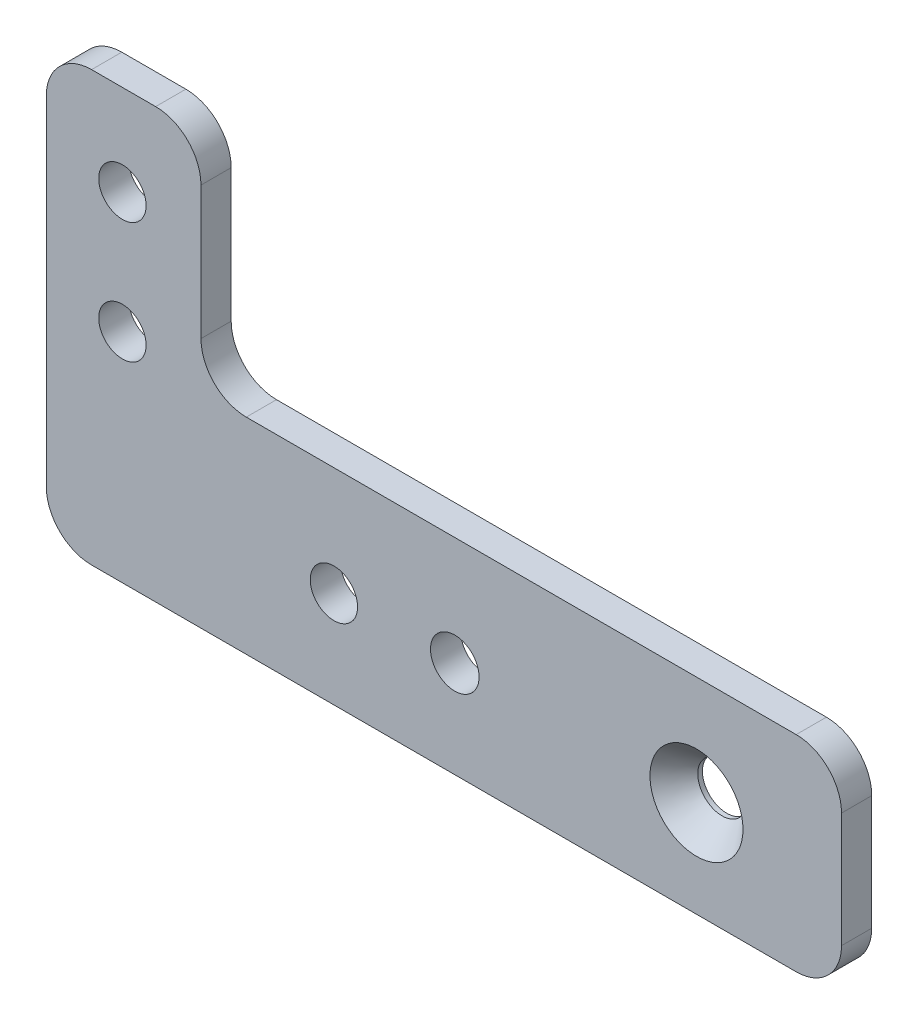
SolidWorks part; units mm, degrees
material "6061-T6 (SS)"
ref_plane "Front Plane" through (0, 0, 0) normal (0, 0, 1) x (1, 0, 0)
ref_plane "Top Plane" through (0, 0, 0) normal (0, 1, 0) x (1, 0, 0)
ref_plane "Right Plane" through (0, 0, 0) normal (1, 0, 0) x (0, 0, -1)
sketch "Sketch1" plane through (0, 0, 0) normal (0, 0, 1) x (1, 0, 0)
  line L0 (-21.59, 23.8125) -> (-37.846, 23.8125) construction
  line L1 (-45.72, -23.8125) -> (45.72, -23.8125)
  line L2 (-45.72, -23.8125) -> (-45.72, 23.8125)
  line L3 (-45.72, 23.8125) -> (45.72, 23.8125)
  line L4 (45.72, -23.8125) -> (45.72, 23.8125)
  line L5 (-45.72, -23.8125) -> (45.72, 23.8125) construction
  line L6 (-45.72, 23.8125) -> (45.72, -23.8125) construction
  line L7 (45.72, 23.8125) -> (-21.59, 23.8125)
  line L8 (45.72, 23.8125) -> (45.72, 0.3175)
  line L9 (45.72, 0.3175) -> (-21.59, 0.3175)
  line L10 (-21.59, 23.8125) -> (-21.59, 0.3175)
  line L11 (-45.72, -23.8125) -> (-37.846, -23.8125)
  line L12 (-45.72, -23.8125) -> (-45.72, 23.8125)
  line L13 (-45.72, 23.8125) -> (-37.846, 23.8125)
  line L14 (-37.846, -23.8125) -> (-37.846, 23.8125)
  line L15 (-37.846, -23.8125) -> (45.72, -23.8125)
  line L16 (-37.846, -23.8125) -> (-37.846, -21.2725)
  line L17 (-37.846, -21.2725) -> (45.72, -21.2725)
  line L18 (45.72, -23.8125) -> (45.72, -21.2725)
  line L19 (-21.59, 23.8125) -> (-37.846, 23.8125) construction
  line L20 (-29.845, 23.8125) -> (-29.845, -21.2725) construction
  circle A0 centre (-29.845, -11.1125) radius 2.4892
  circle A1 centre (-29.845, 1.5875) radius 2.4892
  circle A2 centre (-29.845, 14.2875) radius 2.4892
  circle A4 centre (-7.62, -11.1125) radius 2.4892
  circle A5 centre (5.08, -11.1125) radius 2.5527
  circle A7 centre (30.48, -11.1125) radius 2.5527
  point P0 (0, 0)
  dimension "D7" = 22.225
  dimension "D18" = 5.1054
  dimension "D19" = 4.9784
  dimension "D13" = 25.4
  dimension "D8" = 50.8
  dimension "D1" = 91.44
  dimension "D2" = 9.525
  dimension "D3" = 24.13
  dimension "D4" = 24.13
  dimension "D5" = 7.874
  dimension "D6" = 47.625
  dimension "D9" = 12.7
  dimension "D10" = 12.7
  dimension "D11" = 12.7
  dimension "D12" = 15.875
  dimension "D16" = 2.54
extrude "Boss-Extrude1" add sketch "Sketch1" along normal blind 3.175 contours L14 L17 L4 L9 L10 L3 A5 A4 A2 A1 A0 | A0 region at (-1.4918, -6.6351, 0) region at (-29.845, -11.1125, 0)
fillet "Fillet1" radius 4.7625 6 edges at (-37.846, 23.8125, 1.5875) (-21.59, 23.8125, 1.5875) (-21.59, 0.3175, 1.5875) (45.72, 0.3175, 1.5875) (45.72, -21.2725, 1.5875) (-37.846, -21.2725, 1.5875)
hole_wizard "CSK for #10 Flat Head Machine Screw1" positions "Sketch3" profile "Sketch4" countersink size "#10" standard "ANSI Inch"
sketch "Sketch3" plane through (0, 0, 3.175) normal (0, 0, 1) x (1, 0, 0)
  point P0 (30.48, -11.1125)
sketch "Sketch4" plane through (30.48, -11.1125, 3.175) normal (1, 0, 0) x (0, -1, 0)
  line L0 (0, 0) -> (0, 20.5838)
  line L1 (0, 20.5838) -> (2.5527, 19.05)
  line L2 (2.5527, 19.05) -> (2.5527, 2.6882)
  line L3 (2.5527, 2.6882) -> (4.8895, 0)
  line L5 (4.8895, 0) -> (0, 0)
  line L6 (-2.5527, 2.6882) -> (-4.8895, 0) construction
  line L10 (0, 20.5838) -> (-2.5527, 19.05) construction
  line L11 (0, -6.35) -> (0, 107.95) construction
  dimension "Hole Dia." = 5.1054
  dimension "Hole Depth" = 19.05
  dimension "Near C'Sink Dia." = 9.779
  dimension "Near C'Sink Angle" = 82
  dimension "Drill Angle" = 118
